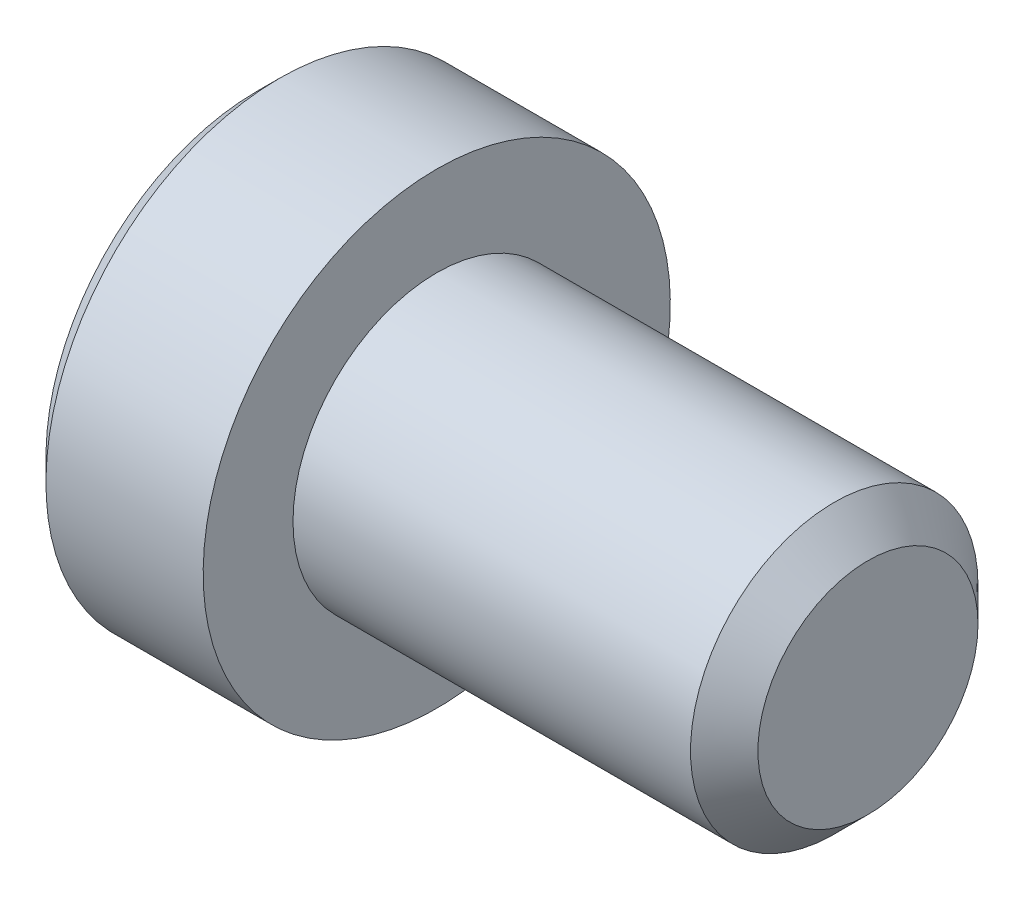
SolidWorks part; units mm, degrees
ref_plane "Front Plane" through (0, 0, 0) normal (0, 0, 1) x (1, 0, 0)
ref_plane "Top Plane" through (0, 0, 0) normal (0, 1, 0) x (1, 0, 0)
ref_plane "Right Plane" through (0, 0, 0) normal (1, 0, 0) x (0, 0, -1)
sketch "Sketch1" plane through (0, 0, 0) normal (0, 0, 1) x (1, 0, 0)
  line L0 (6, 0) -> (-6, 0) construction
  line L1 (6, 4) -> (6, -4) construction
  line L2 (-6, 6.5) -> (-6, -6.5) construction
  line L3 (-6, 6.5) -> (-10.375, 6.5) construction
  line L4 (-10.375, 6.5) -> (-11, 5.875) construction
  line L5 (-11, 5.875) -> (-11, -5.875) construction
  line L6 (-11, -5.875) -> (-10.375, -6.5) construction
  line L7 (-10.375, -6.5) -> (-6, -6.5) construction
  point P7 (-7.05, 0)
  point P12 (1, -4)
  dimension "D1" = 45
  dimension "Dec." = 8
  dimension "Length" = 12
  dimension "Head Dia" = 13
  dimension "Head Height" = 5
  dimension "Hex Depth" = 3.95
  dimension "Chamfer" = 0.625
  dimension "D2" = 5
ref_plane "Plane1" through (6, 0, 0) normal (1, 0, 0) x (0, 0, -1)
ref_plane "Plane2" through (-11, 0, 0) normal (1, 0, 0) x (0, 0, -1)
sketch "Sketch2" plane through (6, 0, 0) normal (1, 0, 0) x (0, 0, -1)
  circle A0 centre (0, 0) radius 4
extrude "Boss-Extrude1" add sketch "Sketch2" against normal up to vertex (12 mm away) up to point (-6, 0, 0)
sketch "Sketch3" plane through (6, 0, 0) normal (1, 0, 0) x (0, 0, -1)
  circle A0 centre (0, 0) radius 4 construction
  circle A1 centre (0, 0) radius 4
curve "Helix/Spiral1" pitch 1.25 height 13.25 turns 10.6 parameters "Pitch"=1.25
chamfer "Chamfer1" distance 0.9375 angle 45 1 edges at (6, 0, -4)
sketch "Sketch5" plane through (0, 0, 0) normal (0, 0, 1) x (1, 0, 0)
  line L0 (5.4531, 4) -> (6.5469, 4)
  line L1 (6.5469, 4) -> (6.0781, 3.1881)
  line L2 (6.0781, 3.1881) -> (5.9219, 3.1881)
  line L3 (5.9219, 3.1881) -> (5.4531, 4)
  line L4 (6, 3.1881) -> (6, 4) construction
  line L5 (5.6875, 3.5941) -> (6.3125, 3.5941) construction
  dimension "D1" = 60
  dimension "D2" = 0.625
  dimension "D3" = 0.1562
sweep "Cut-Sweep1" [suppressed] cut profiles "Sketch5" path "Helix/Spiral1"
sketch "Sketch4" plane through (-11, 0, 0) normal (1, 0, 0) x (0, 0, -1)
  line L0 (-6.5, 0.7937) -> (6.5, 0.7937) construction
  line L1 (0, 2.8868) -> (-2.5, 1.4434)
  line L2 (-2.5, 1.4434) -> (-2.5, -1.4434)
  line L3 (-2.5, -1.4434) -> (0, -2.8868)
  line L4 (0, -2.8868) -> (2.5, -1.4434)
  line L5 (2.5, -1.4434) -> (2.5, 1.4434)
  line L6 (2.5, 1.4434) -> (0, 2.8868)
  line L7 (0, 0) -> (0, 0.7937) construction
  circle A0 centre (0, 0) radius 2.5 construction
  dimension "Hex Size" = 5
  dimension "D1" = 13
  dimension "D2" = 0.7937
sketch "Sketch6" plane through (0, 0, 0) normal (0, 0, 1) x (1, 0, 0)
  line L0 (-10.375, 6.5) -> (-11, 5.875) construction
  line L1 (-6, 6.5) -> (-10.375, 6.5) construction
  line L2 (-6, 6.5) -> (-6, -6.5) construction
  line L3 (-11, 5.875) -> (-11, -5.875) construction
  line L4 (-10.375, 6.5) -> (-11, 5.875)
  line L5 (-6, 6.5) -> (-10.375, 6.5)
  line L6 (-6, 6.5) -> (-6, 0)
  line L7 (-11, 5.875) -> (-11, 0)
  line L8 (-6, 0) -> (-11, 0) construction
  line L9 (-6, 0) -> (-11, 0)
revolve "Revolve1" add sketch "Sketch6" angle 360 about L8
extrude "Cut-Extrude1" cut sketch "Sketch4" along normal up to vertex (3.95 mm away) up to point (-7.05, 0, 0)
sketch "Sketch8" plane through (-11, 0, 0) normal (-1, 0, 0) x (0, 0, 1)
  circle A1 centre (0, 0) radius 2.8868
extrude "Cut-Extrude2" cut sketch "Sketch8" against normal through all draft 45
equation "\"D3@Helix/Spiral1\" = \"Length@Sketch1\"+\"Pitch@Helix/Spiral1\""
equation "\"D3@Sketch5\" = \"Pitch@Helix/Spiral1\"*.125"
equation "\"D2@Sketch5\" = \"Pitch@Helix/Spiral1\"*.50"
equation "\"D1@Chamfer1\" = \"Pitch@Helix/Spiral1\"*.75"
equation "\"D2@Sketch1\" = \"Pitch@Helix/Spiral1\"*4"
equation "\"D1@Sketch4\" = \"Head Dia@Sketch1\""
equation "\"Chamfer@Sketch1\" = \"Head Height@Sketch1\"/8"
